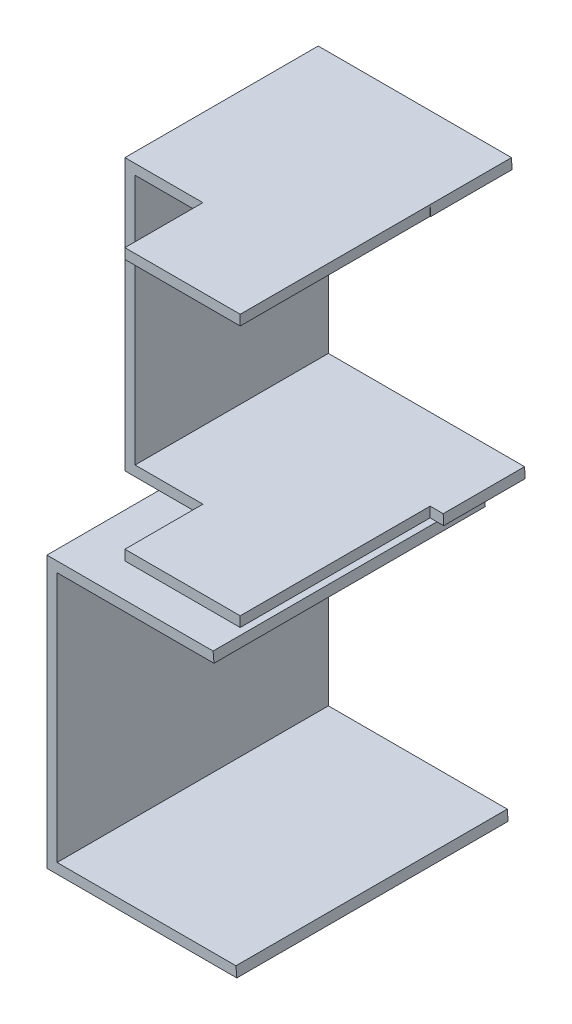
SolidWorks part; units mm, degrees
ref_plane "정면" through (0, 0, 0) normal (0, 0, 1) x (1, 0, 0)
ref_plane "윗면" through (0, 0, 0) normal (0, 1, 0) x (1, 0, 0)
ref_plane "우측면" through (0, 0, 0) normal (1, 0, 0) x (0, 0, -1)
sketch "스케치1" plane through (0, 0, 0) normal (0, 0, 1) x (1, 0, 0)
  line L0 (0, 0) -> (61, 0)
  line L2 (57, 80) -> (0, 80)
  line L3 (0, 80) -> (0, 0)
  line L4 (57.15, 77) -> (3, 77)
  line L5 (3, 77) -> (3, 3)
  line L6 (3, 3) -> (60.85, 3)
  line L9 (61, 0) -> (60.85, 3)
  line L10 (57.15, 77) -> (57, 80)
  line L11 (0, -10) -> (49, -10)
  line L12 (0, -10) -> (0, -90)
  line L13 (0, -90) -> (56, -90)
  line L15 (49.2625, -13) -> (3, -13)
  line L16 (3, -13) -> (3, -87)
  line L17 (3, -87) -> (55.7375, -87)
  line L18 (49.2625, -13) -> (49, -10)
  line L19 (55.7375, -87) -> (56, -90)
  line L20 (0, 140.1376) -> (0, -278.5402) construction
  line L21 (-165.7064, 0) -> (202.0952, 0) construction
  dimension "D1" = 80
  dimension "D2" = 61
  dimension "D3" = 57
  dimension "D4" = 3
  dimension "D5" = 3
  dimension "D6" = 3
  dimension "D7" = 80
  dimension "D8" = 49
  dimension "D9" = 56
  dimension "D10" = 10
  dimension "D11" = 3
  dimension "D12" = 3
  dimension "D13" = 3
extrude "보스-돌출1" add sketch "스케치1" along normal blind 80 contours L6 L9 L0 L3 L2 L10 L4 L5
extrude "보스-돌출2" add sketch "스케치1<3>" along normal blind 80 separate body contours L13 L19 L17 L16 L15 L18 L11 L12
sketch "스케치1<3>" plane through (0, 0, 0) normal (0, 0, 1) x (1, 0, 0) same geometry as "스케치1"
sketch "스케치4" plane through (0, 80, 0) normal (0, 1, 0) x (1, 0, 0)
  line L0 (0, -80) -> (23, -80)
  line L1 (57, -80) -> (0, -80) construction
  line L2 (23, -80) -> (23, -57)
  line L3 (23, -57) -> (0, -57)
  line L4 (0, -80) -> (0, 0) construction
  line L5 (0, -57) -> (0, -80)
  dimension "D1" = 23
  dimension "D2" = 23
extrude "컷-돌출5" cut sketch "스케치4" against normal blind 80
sketch "스케치5" plane through (0, 80, 0) normal (0, 1, 0) x (1, 0, 0)
  line L0 (57, -80) -> (61, -80)
  line L1 (61, -80) -> (61, -24)
  line L2 (61, -80) -> (61, 0) construction
  line L3 (61, -24) -> (57, -24)
  line L4 (57, -80) -> (57, 0) construction
  line L5 (57, -24) -> (57, -80)
  dimension "D1" = 56
extrude "컷-돌출7" cut sketch "스케치5" against normal blind 80
